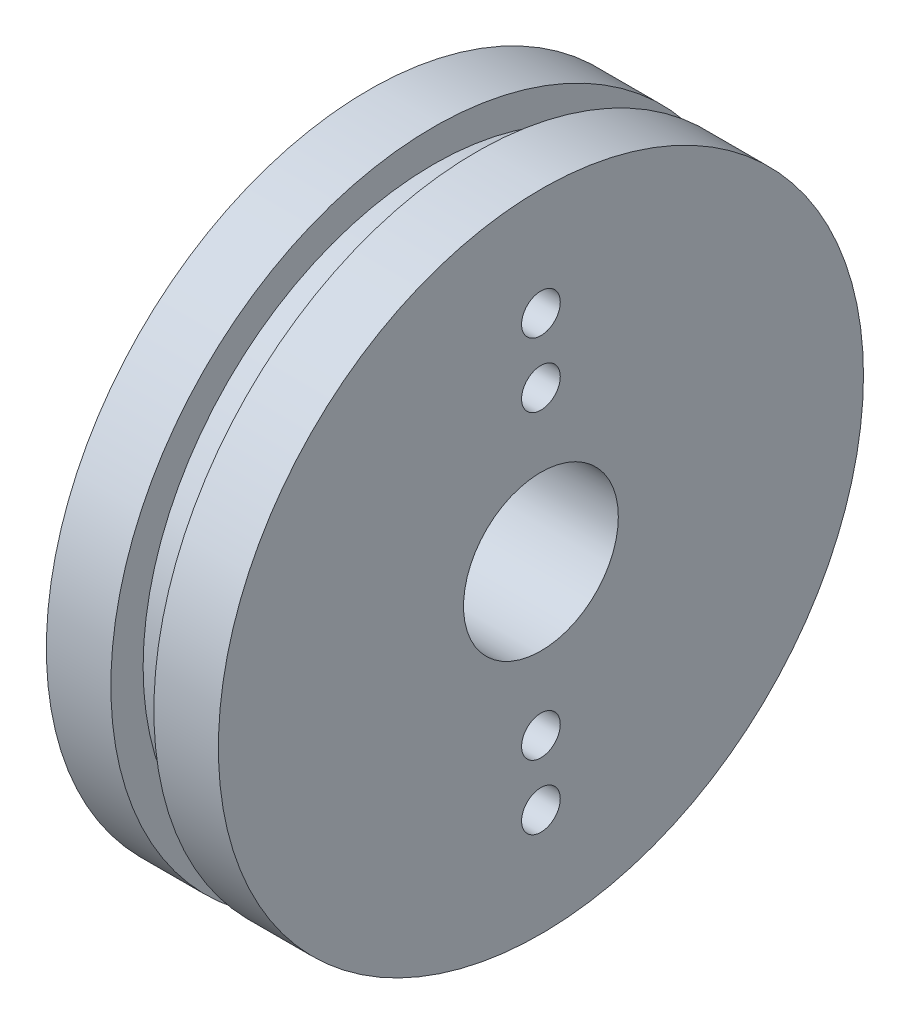
SolidWorks part; units mm, degrees
ref_plane "Front Plane" through (0, 0, 0) normal (0, 0, 1) x (1, 0, 0)
ref_plane "Top Plane" through (0, 0, 0) normal (0, 1, 0) x (1, 0, 0)
ref_plane "Right Plane" through (0, 0, 0) normal (1, 0, 0) x (0, 0, -1)
sketch "Sketch1" plane through (0, 0, 0) normal (1, 0, 0) x (0, 0, -1)
  circle A0 centre (0, 0) radius 15
extrude "Boss-Extrude1" add sketch "Sketch1" along normal blind 8
sketch "Sketch2" plane through (0, 0, 0) normal (1, 0, 0) x (0, 0, -1)
  circle A0 centre (0, 0) radius 16
extrude "Boss-Extrude2" add sketch "Sketch2" along normal blind 2 from offset 3 separate body
combine bodies "Combine1" operation type subtract main body 101 bodies to subtract 102
sketch "Sketch3" plane through (0, 0, 0) normal (1, 0, 0) x (0, 0, -1)
  circle A0 centre (0, 0) radius 13.5
extrude "Boss-Extrude3" add sketch "Sketch3" along normal blind 2 from offset 3
sketch "Sketch4" plane through (0, 0, 0) normal (1, 0, 0) x (0, 0, -1)
  circle A0 centre (0, 0) radius 3.6
extrude "Boss-Extrude4" add sketch "Sketch4" along normal blind 10 from offset 1 separate body offset against normal yes
combine bodies "Combine2" operation type subtract main body 105 bodies to subtract 106
sketch "Sketch5" plane through (0, 0, 0) normal (1, 0, 0) x (0, 0, -1)
  circle A0 centre (0, -10) radius 0.9
extrude "Boss-Extrude5" add sketch "Sketch5" along normal blind 10 from offset 1 separate body offset against normal yes
combine bodies "Combine3" operation type subtract main body 107 bodies to subtract 108
sketch "Sketch6" plane through (0, 0, 0) normal (1, 0, 0) x (0, 0, -1)
  circle A0 centre (0, -7) radius 0.9
extrude "Boss-Extrude6" add sketch "Sketch6" along normal blind 10 from offset 1 separate body offset against normal yes
combine bodies "Combine4" operation type subtract main body 109 bodies to subtract 110
sketch "Sketch7" plane through (0, 0, 0) normal (1, 0, 0) x (0, 0, -1)
  circle A0 centre (0, 7) radius 0.9
extrude "Boss-Extrude7" add sketch "Sketch7" along normal blind 10 from offset 1 separate body offset against normal yes
combine bodies "Combine5" operation type subtract main body 111 bodies to subtract 112
sketch "Sketch8" plane through (0, 0, 0) normal (1, 0, 0) x (0, 0, -1)
  circle A0 centre (0, 10) radius 0.9
extrude "Boss-Extrude8" add sketch "Sketch8" along normal blind 10 from offset 1 separate body offset against normal yes
combine bodies "Combine6" operation type subtract main body 113 bodies to subtract 114
